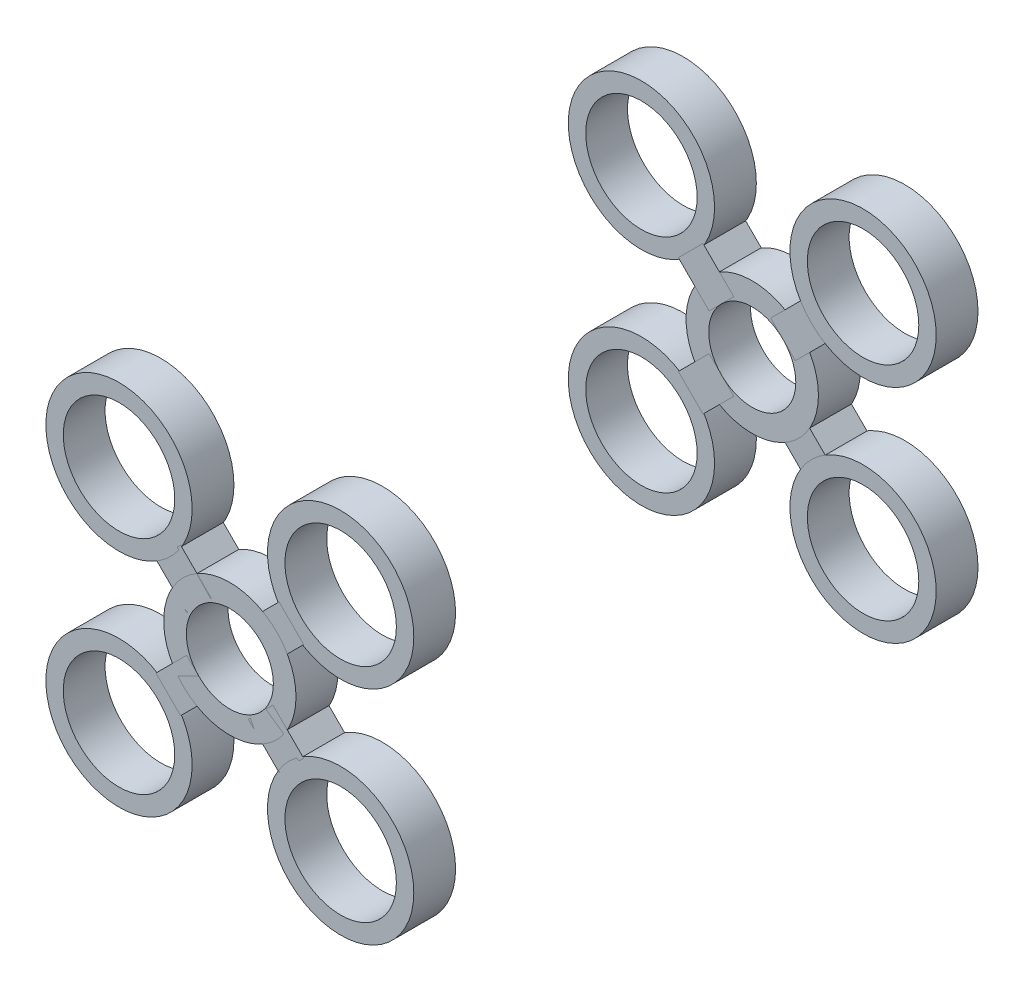
SolidWorks part; units mm, degrees
material "POM Acetal Copolymer"
ref_plane "Front Plane" through (0, 0, 0) normal (0, 0, 1) x (1, 0, 0)
ref_plane "Top Plane" through (0, 0, 0) normal (0, 1, 0) x (1, 0, 0)
ref_plane "Right Plane" through (0, 0, 0) normal (1, 0, 0) x (0, 0, -1)
sketch "Extrude sketch 1" plane through (0, 0, 0) normal (0, 0, 1) x (1, 0, 0)
  circle A0 centre (271.8198, 31.8198) radius 21
  circle A1 centre (271.8198, 31.8198) radius 16
  dimension "D1" = 32
  dimension "D2" = 42
extrude "Extrude 1" add sketch "Extrude sketch 1" along normal blind 12 from offset 62 separate body
sketch "Extrude sketch 2" plane through (0, 0, 0) normal (0, 0, 1) x (1, 0, 0)
  line L0 (252.3744, 5.3033) -> (261.2132, 14.1421)
  line L1 (261.2132, 14.1421) -> (254.1421, 21.2132)
  line L2 (254.1421, 21.2132) -> (245.3033, 12.3744)
  line L3 (245.3033, 12.3744) -> (252.3744, 5.3033)
  dimension "D1" = 7.0711
  dimension "D2" = 8.8388
  dimension "D3" = 7.0711
extrude "Extrude 2" add sketch "Extrude sketch 2" along normal blind 12 from offset 62 separate body
sketch "Extrude sketch 3" plane through (0, 0, 0) normal (0, 0, 1) x (1, 0, 0)
  circle A0 centre (208.1802, 31.8198) radius 21
  circle A1 centre (208.1802, 31.8198) radius 16
  dimension "D1" = 32
  dimension "D2" = 42
extrude "Extrude 3" add sketch "Extrude sketch 3" along normal blind 12 from offset 62 separate body
sketch "Extrude sketch 4" plane through (0, 0, 0) normal (0, 0, 1) x (1, 0, 0)
  line L0 (234.6967, 12.3744) -> (225.8579, 21.2132)
  line L1 (225.8579, 21.2132) -> (218.7868, 14.1421)
  line L2 (218.7868, 14.1421) -> (227.6256, 5.3033)
  line L3 (227.6256, 5.3033) -> (234.6967, 12.3744)
  dimension "D1" = 7.0711
  dimension "D2" = 8.8388
  dimension "D3" = 7.0711
extrude "Extrude 4" add sketch "Extrude sketch 4" along normal blind 12 from offset 62 separate body
sketch "Extrude sketch 5" plane through (0, 0, 0) normal (0, 0, 1) x (1, 0, 0)
  circle A0 centre (208.1802, -31.8198) radius 21
  circle A1 centre (208.1802, -31.8198) radius 16
  dimension "D1" = 32
  dimension "D2" = 42
extrude "Extrude 5" add sketch "Extrude sketch 5" along normal blind 12 from offset 62 separate body
sketch "Extrude sketch 6" plane through (0, 0, 0) normal (0, 0, 1) x (1, 0, 0)
  line L0 (227.6256, -5.3033) -> (218.7868, -14.1421)
  line L1 (218.7868, -14.1421) -> (225.8579, -21.2132)
  line L2 (225.8579, -21.2132) -> (234.6967, -12.3744)
  line L3 (234.6967, -12.3744) -> (227.6256, -5.3033)
  dimension "D1" = 7.0711
  dimension "D2" = 8.8388
  dimension "D3" = 7.0711
extrude "Extrude 6" add sketch "Extrude sketch 6" along normal blind 12 from offset 62 separate body
sketch "Extrude sketch 7" plane through (0, 0, 0) normal (0, 0, 1) x (1, 0, 0)
  circle A0 centre (271.8198, -31.8198) radius 21
  circle A1 centre (271.8198, -31.8198) radius 16
  dimension "D1" = 32
  dimension "D2" = 42
extrude "Extrude 7" add sketch "Extrude sketch 7" along normal blind 12 from offset 62 separate body
sketch "Extrude sketch 8" plane through (0, 0, 0) normal (0, 0, 1) x (1, 0, 0)
  line L0 (245.3033, -12.3744) -> (254.1421, -21.2132)
  line L1 (254.1421, -21.2132) -> (261.2132, -14.1421)
  line L2 (261.2132, -14.1421) -> (252.3744, -5.3033)
  line L3 (252.3744, -5.3033) -> (245.3033, -12.3744)
  dimension "D1" = 7.0711
  dimension "D2" = 8.8388
  dimension "D3" = 7.0711
extrude "Extrude 8" add sketch "Extrude sketch 8" along normal blind 12 from offset 62 separate body
sketch "Extrude sketch 9" plane through (0, 0, 0) normal (0, 0, 1) x (1, 0, 0)
  circle A0 centre (240, 0) radius 19
  circle A1 centre (240, 0) radius 12.5
  dimension "D1" = 25
  dimension "D2" = 38
extrude "Extrude 9" add sketch "Extrude sketch 9" along normal blind 12 from offset 62 separate body
sketch "Extrude sketch 10" plane through (0, 0, 0) normal (0, 0, 1) x (1, 0, 0)
  circle A0 centre (271.8198, 31.8198) radius 21
  circle A1 centre (271.8198, 31.8198) radius 16
  dimension "D1" = 32
  dimension "D2" = 42
extrude "Extrude 10" add sketch "Extrude sketch 10" along normal blind 12 from offset 212 separate body
sketch "Extrude sketch 11" plane through (0, 0, 0) normal (0, 0, 1) x (1, 0, 0)
  line L0 (252.3744, 5.3033) -> (261.2132, 14.1421)
  line L1 (261.2132, 14.1421) -> (254.1421, 21.2132)
  line L2 (254.1421, 21.2132) -> (245.3033, 12.3744)
  line L3 (245.3033, 12.3744) -> (252.3744, 5.3033)
  dimension "D1" = 7.0711
  dimension "D2" = 8.8388
  dimension "D3" = 7.0711
extrude "Extrude 11" add sketch "Extrude sketch 11" along normal blind 12 from offset 212 separate body
sketch "Extrude sketch 12" plane through (0, 0, 0) normal (0, 0, 1) x (1, 0, 0)
  circle A0 centre (208.1802, 31.8198) radius 21
  circle A1 centre (208.1802, 31.8198) radius 16
  dimension "D1" = 32
  dimension "D2" = 42
extrude "Extrude 12" add sketch "Extrude sketch 12" along normal blind 12 from offset 212 separate body
sketch "Extrude sketch 13" plane through (0, 0, 0) normal (0, 0, 1) x (1, 0, 0)
  line L0 (234.6967, 12.3744) -> (225.8579, 21.2132)
  line L1 (225.8579, 21.2132) -> (218.7868, 14.1421)
  line L2 (218.7868, 14.1421) -> (227.6256, 5.3033)
  line L3 (227.6256, 5.3033) -> (234.6967, 12.3744)
  dimension "D1" = 7.0711
  dimension "D2" = 8.8388
  dimension "D3" = 7.0711
extrude "Extrude 13" add sketch "Extrude sketch 13" along normal blind 12 from offset 212 separate body
sketch "Extrude sketch 14" plane through (0, 0, 0) normal (0, 0, 1) x (1, 0, 0)
  circle A0 centre (208.1802, -31.8198) radius 21
  circle A1 centre (208.1802, -31.8198) radius 16
  dimension "D1" = 32
  dimension "D2" = 42
extrude "Extrude 14" add sketch "Extrude sketch 14" along normal blind 12 from offset 212 separate body
sketch "Extrude sketch 15" plane through (0, 0, 0) normal (0, 0, 1) x (1, 0, 0)
  line L0 (227.6256, -5.3033) -> (218.7868, -14.1421)
  line L1 (218.7868, -14.1421) -> (225.8579, -21.2132)
  line L2 (225.8579, -21.2132) -> (234.6967, -12.3744)
  line L3 (234.6967, -12.3744) -> (227.6256, -5.3033)
  dimension "D1" = 7.0711
  dimension "D2" = 8.8388
  dimension "D3" = 7.0711
extrude "Extrude 15" add sketch "Extrude sketch 15" along normal blind 12 from offset 212 separate body
sketch "Extrude sketch 16" plane through (0, 0, 0) normal (0, 0, 1) x (1, 0, 0)
  circle A0 centre (271.8198, -31.8198) radius 21
  circle A1 centre (271.8198, -31.8198) radius 16
  dimension "D1" = 32
  dimension "D2" = 42
extrude "Extrude 16" add sketch "Extrude sketch 16" along normal blind 12 from offset 212 separate body
sketch "Extrude sketch 17" plane through (0, 0, 0) normal (0, 0, 1) x (1, 0, 0)
  line L0 (245.3033, -12.3744) -> (254.1421, -21.2132)
  line L1 (254.1421, -21.2132) -> (261.2132, -14.1421)
  line L2 (261.2132, -14.1421) -> (252.3744, -5.3033)
  line L3 (252.3744, -5.3033) -> (245.3033, -12.3744)
  dimension "D1" = 7.0711
  dimension "D2" = 8.8388
  dimension "D3" = 7.0711
extrude "Extrude 17" add sketch "Extrude sketch 17" along normal blind 12 from offset 212 separate body
sketch "Extrude sketch 18" plane through (0, 0, 0) normal (0, 0, 1) x (1, 0, 0)
  circle A0 centre (240, 0) radius 19
  circle A1 centre (240, 0) radius 12.5
  dimension "D1" = 25
  dimension "D2" = 38
extrude "Extrude 18" add sketch "Extrude sketch 18" along normal blind 12 from offset 212 separate body
